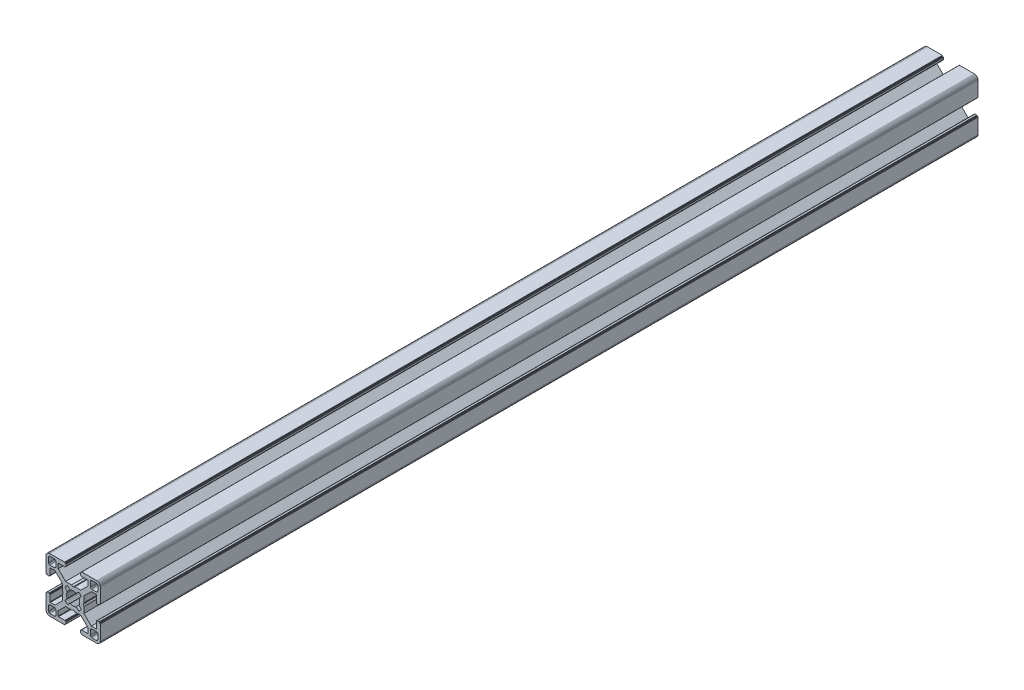
SolidWorks part; units mm, degrees
ref_plane "Front Plane" through (0, 0, 0) normal (0, 0, 1) x (1, 0, 0)
ref_plane "Top Plane" through (0, 0, 0) normal (0, 1, 0) x (1, 0, 0)
ref_plane "Right Plane" through (0, 0, 0) normal (1, 0, 0) x (0, 0, -1)
ref_plane "Plane1" through (0, 0, 0) normal (0, 0, 1) x (1, 0, 0)
sketch "Sketch1" plane through (0, 0, 0) normal (0, 0, 1) x (1, 0, 0)
  line L0 (28.3473, 29.9696) -> (28, 30)
  line L1 (28, 30) -> (19.75, 30)
  line L2 (19.75, 30) -> (19.7153, 29.997)
  line L3 (19.7153, 29.997) -> (19.6816, 29.9879)
  line L4 (19.6816, 29.9879) -> (19.65, 29.9732)
  line L5 (19.65, 29.9732) -> (19.6214, 29.9532)
  line L6 (19.6214, 29.9532) -> (19.5968, 29.9286)
  line L7 (19.5968, 29.9286) -> (19.5768, 29.9)
  line L8 (19.5768, 29.9) -> (19.5621, 29.8684)
  line L9 (19.5621, 29.8684) -> (19.553, 29.8347)
  line L10 (19.553, 29.8347) -> (19.55, 29.8)
  line L11 (19.55, 29.8) -> (19.55, 29.7)
  line L12 (19.55, 29.7) -> (19.547, 29.6653)
  line L13 (19.547, 29.6653) -> (19.5379, 29.6316)
  line L14 (19.5379, 29.6316) -> (19.5232, 29.6)
  line L15 (19.5232, 29.6) -> (19.5032, 29.5714)
  line L16 (19.5032, 29.5714) -> (19.4786, 29.5468)
  line L17 (19.4786, 29.5468) -> (19.45, 29.5268)
  line L18 (19.45, 29.5268) -> (19.4184, 29.5121)
  line L19 (19.4184, 29.5121) -> (19.3847, 29.503)
  line L20 (19.3847, 29.503) -> (19.35, 29.5)
  line L21 (19.35, 29.5) -> (19.25, 29.5)
  line L22 (19.25, 29.5) -> (19.2153, 29.497)
  line L23 (19.2153, 29.497) -> (19.1816, 29.4879)
  line L24 (19.1816, 29.4879) -> (19.15, 29.4732)
  line L25 (19.15, 29.4732) -> (19.1214, 29.4532)
  line L26 (19.1214, 29.4532) -> (19.0968, 29.4286)
  line L27 (19.0968, 29.4286) -> (19.0768, 29.4)
  line L28 (19.0768, 29.4) -> (19.0621, 29.3684)
  line L29 (19.0621, 29.3684) -> (19.053, 29.3347)
  line L30 (19.053, 29.3347) -> (19.05, 29.3)
  line L31 (19.05, 29.3) -> (19.05, 28.4)
  line L32 (19.05, 28.4) -> (19.0591, 28.2958)
  line L33 (19.0591, 28.2958) -> (19.0862, 28.1948)
  line L34 (19.0862, 28.1948) -> (19.1304, 28.1)
  line L35 (19.1304, 28.1) -> (19.1904, 28.0143)
  line L36 (19.1904, 28.0143) -> (19.2643, 27.9404)
  line L37 (19.2643, 27.9404) -> (19.35, 27.8804)
  line L38 (19.35, 27.8804) -> (19.4448, 27.8362)
  line L39 (19.4448, 27.8362) -> (19.5458, 27.8091)
  line L40 (19.5458, 27.8091) -> (19.65, 27.8)
  line L41 (19.65, 27.8) -> (23.05, 27.8)
  line L42 (23.05, 27.8) -> (23.0847, 27.7969)
  line L43 (23.0847, 27.7969) -> (23.1184, 27.7879)
  line L44 (23.1184, 27.7879) -> (23.15, 27.7732)
  line L45 (23.15, 27.7732) -> (23.1786, 27.7532)
  line L46 (23.1786, 27.7532) -> (23.2032, 27.7285)
  line L47 (23.2032, 27.7285) -> (23.2232, 27.7)
  line L48 (23.2232, 27.7) -> (23.2379, 27.6684)
  line L49 (23.2379, 27.6684) -> (23.247, 27.6347)
  line L50 (23.247, 27.6347) -> (23.25, 27.6)
  line L51 (23.25, 27.6) -> (23.25, 25.05)
  line L52 (23.25, 25.05) -> (19.2045, 21)
  line L53 (19.2045, 21) -> (15.9, 21)
  line L54 (15.9, 21) -> (15, 20.4848)
  line L55 (15, 20.4848) -> (14.1, 21)
  line L56 (14.1, 21) -> (10.7955, 21)
  line L57 (10.7955, 21) -> (7.9973, 23.8013)
  line L58 (7.9973, 23.8013) -> (6.75, 25.05)
  line L59 (6.75, 25.05) -> (6.75, 27.6)
  line L60 (6.75, 27.6) -> (6.753, 27.6347)
  line L61 (6.753, 27.6347) -> (6.7621, 27.6684)
  line L62 (6.7621, 27.6684) -> (6.7768, 27.7)
  line L63 (6.7768, 27.7) -> (6.7968, 27.7285)
  line L64 (6.7968, 27.7285) -> (6.8215, 27.7532)
  line L65 (6.8215, 27.7532) -> (6.85, 27.7732)
  line L66 (6.85, 27.7732) -> (6.8816, 27.7879)
  line L67 (6.8816, 27.7879) -> (6.9153, 27.7969)
  line L68 (6.9153, 27.7969) -> (6.95, 27.8)
  line L69 (6.95, 27.8) -> (10.35, 27.8)
  line L70 (10.35, 27.8) -> (10.4542, 27.8091)
  line L71 (10.4542, 27.8091) -> (10.5552, 27.8362)
  line L72 (10.5552, 27.8362) -> (10.65, 27.8804)
  line L73 (10.65, 27.8804) -> (10.7357, 27.9404)
  line L74 (10.7357, 27.9404) -> (10.8096, 28.0143)
  line L75 (10.8096, 28.0143) -> (10.8696, 28.1)
  line L76 (10.8696, 28.1) -> (10.9138, 28.1948)
  line L77 (10.9138, 28.1948) -> (10.9409, 28.2958)
  line L78 (10.9409, 28.2958) -> (10.95, 28.4)
  line L79 (10.95, 28.4) -> (10.95, 29.3)
  line L80 (10.95, 29.3) -> (10.947, 29.3347)
  line L81 (10.947, 29.3347) -> (10.938, 29.3684)
  line L82 (10.938, 29.3684) -> (10.9232, 29.4)
  line L83 (10.9232, 29.4) -> (10.9032, 29.4286)
  line L84 (10.9032, 29.4286) -> (10.8786, 29.4532)
  line L85 (10.8786, 29.4532) -> (10.85, 29.4732)
  line L86 (10.85, 29.4732) -> (10.8184, 29.4879)
  line L87 (10.8184, 29.4879) -> (10.7847, 29.497)
  line L88 (10.7847, 29.497) -> (10.75, 29.5)
  line L89 (10.75, 29.5) -> (10.65, 29.5)
  line L90 (10.65, 29.5) -> (10.6153, 29.503)
  line L91 (10.6153, 29.503) -> (10.5816, 29.5121)
  line L92 (10.5816, 29.5121) -> (10.55, 29.5268)
  line L93 (10.55, 29.5268) -> (10.5214, 29.5468)
  line L94 (10.5214, 29.5468) -> (10.4968, 29.5714)
  line L95 (10.4968, 29.5714) -> (10.4768, 29.6)
  line L96 (10.4768, 29.6) -> (10.4621, 29.6316)
  line L97 (10.4621, 29.6316) -> (10.453, 29.6653)
  line L98 (10.453, 29.6653) -> (10.45, 29.7)
  line L99 (10.45, 29.7) -> (10.45, 29.8)
  line L100 (10.45, 29.8) -> (10.447, 29.8347)
  line L101 (10.447, 29.8347) -> (10.4379, 29.8684)
  line L102 (10.4379, 29.8684) -> (10.4232, 29.9)
  line L103 (10.4232, 29.9) -> (10.4032, 29.9286)
  line L104 (10.4032, 29.9286) -> (10.3786, 29.9532)
  line L105 (10.3786, 29.9532) -> (10.35, 29.9732)
  line L106 (10.35, 29.9732) -> (10.3184, 29.9879)
  line L107 (10.3184, 29.9879) -> (10.2847, 29.997)
  line L108 (10.2847, 29.997) -> (10.25, 30)
  line L109 (10.25, 30) -> (2, 30)
  line L110 (2, 30) -> (1.6527, 29.9696)
  line L111 (1.6527, 29.9696) -> (1.316, 29.8794)
  line L112 (1.316, 29.8794) -> (1, 29.7321)
  line L113 (1, 29.7321) -> (0.7144, 29.5321)
  line L114 (0.7144, 29.5321) -> (0.4679, 29.2856)
  line L115 (0.4679, 29.2856) -> (0.2679, 29)
  line L116 (0.2679, 29) -> (0.1206, 28.684)
  line L117 (0.1206, 28.684) -> (0.0304, 28.3473)
  line L118 (0.0304, 28.3473) -> (0, 28)
  line L119 (0, 28) -> (0, 19.75)
  line L120 (0, 19.75) -> (0.003, 19.7153)
  line L121 (0.003, 19.7153) -> (0.0121, 19.6816)
  line L122 (0.0121, 19.6816) -> (0.0268, 19.65)
  line L123 (0.0268, 19.65) -> (0.0468, 19.6214)
  line L124 (0.0468, 19.6214) -> (0.0714, 19.5968)
  line L125 (0.0714, 19.5968) -> (0.1, 19.5768)
  line L126 (0.1, 19.5768) -> (0.1316, 19.5621)
  line L127 (0.1316, 19.5621) -> (0.1653, 19.553)
  line L128 (0.1653, 19.553) -> (0.2, 19.55)
  line L129 (0.2, 19.55) -> (0.3, 19.55)
  line L130 (0.3, 19.55) -> (0.3347, 19.547)
  line L131 (0.3347, 19.547) -> (0.3684, 19.5379)
  line L132 (0.3684, 19.5379) -> (0.4, 19.5232)
  line L133 (0.4, 19.5232) -> (0.4286, 19.5032)
  line L134 (0.4286, 19.5032) -> (0.4532, 19.4786)
  line L135 (0.4532, 19.4786) -> (0.4732, 19.45)
  line L136 (0.4732, 19.45) -> (0.4879, 19.4184)
  line L137 (0.4879, 19.4184) -> (0.497, 19.3847)
  line L138 (0.497, 19.3847) -> (0.5, 19.35)
  line L139 (0.5, 19.35) -> (0.5, 19.25)
  line L140 (0.5, 19.25) -> (0.503, 19.2153)
  line L141 (0.503, 19.2153) -> (0.5121, 19.1816)
  line L142 (0.5121, 19.1816) -> (0.5268, 19.15)
  line L143 (0.5268, 19.15) -> (0.5468, 19.1214)
  line L144 (0.5468, 19.1214) -> (0.5714, 19.0968)
  line L145 (0.5714, 19.0968) -> (0.6, 19.0768)
  line L146 (0.6, 19.0768) -> (0.6316, 19.0621)
  line L147 (0.6316, 19.0621) -> (0.6653, 19.053)
  line L148 (0.6653, 19.053) -> (0.7, 19.05)
  line L149 (0.7, 19.05) -> (1.6, 19.05)
  line L150 (1.6, 19.05) -> (1.7042, 19.0591)
  line L151 (1.7042, 19.0591) -> (1.8052, 19.0862)
  line L152 (1.8052, 19.0862) -> (1.9, 19.1304)
  line L153 (1.9, 19.1304) -> (1.9857, 19.1904)
  line L154 (1.9857, 19.1904) -> (2.0596, 19.2643)
  line L155 (2.0596, 19.2643) -> (2.1196, 19.35)
  line L156 (2.1196, 19.35) -> (2.1638, 19.4448)
  line L157 (2.1638, 19.4448) -> (2.1909, 19.5458)
  line L158 (2.1909, 19.5458) -> (2.2, 19.65)
  line L159 (2.2, 19.65) -> (2.2, 23.05)
  line L160 (2.2, 23.05) -> (2.203, 23.0847)
  line L161 (2.203, 23.0847) -> (2.2121, 23.1184)
  line L162 (2.2121, 23.1184) -> (2.2268, 23.15)
  line L163 (2.2268, 23.15) -> (2.2468, 23.1786)
  line L164 (2.2468, 23.1786) -> (2.2714, 23.2032)
  line L165 (2.2714, 23.2032) -> (2.3, 23.2232)
  line L166 (2.3, 23.2232) -> (2.3316, 23.2379)
  line L167 (2.3316, 23.2379) -> (2.3653, 23.247)
  line L168 (2.3653, 23.247) -> (2.4, 23.25)
  line L169 (2.4, 23.25) -> (4.95, 23.25)
  line L170 (4.95, 23.25) -> (7.9973, 20.2027)
  line L171 (7.9973, 20.2027) -> (8.9955, 19.2045)
  line L172 (8.9955, 19.2045) -> (8.9955, 15.9)
  line L173 (8.9955, 15.9) -> (9.5151, 15)
  line L174 (9.5151, 15) -> (8.9955, 14.1)
  line L175 (8.9955, 14.1) -> (8.9955, 10.7955)
  line L176 (8.9955, 10.7955) -> (4.95, 6.75)
  line L177 (4.95, 6.75) -> (2.4, 6.75)
  line L178 (2.4, 6.75) -> (2.3653, 6.753)
  line L179 (2.3653, 6.753) -> (2.3316, 6.7621)
  line L180 (2.3316, 6.7621) -> (2.3, 6.7768)
  line L181 (2.3, 6.7768) -> (2.2714, 6.7968)
  line L182 (2.2714, 6.7968) -> (2.2468, 6.8214)
  line L183 (2.2468, 6.8214) -> (2.2268, 6.85)
  line L184 (2.2268, 6.85) -> (2.2121, 6.8816)
  line L185 (2.2121, 6.8816) -> (2.203, 6.9153)
  line L186 (2.203, 6.9153) -> (2.2, 6.95)
  line L187 (2.2, 6.95) -> (2.2, 10.35)
  line L188 (2.2, 10.35) -> (2.1909, 10.4542)
  line L189 (2.1909, 10.4542) -> (2.1638, 10.5552)
  line L190 (2.1638, 10.5552) -> (2.1196, 10.65)
  line L191 (2.1196, 10.65) -> (2.0596, 10.7357)
  line L192 (2.0596, 10.7357) -> (1.9857, 10.8096)
  line L193 (1.9857, 10.8096) -> (1.9, 10.8696)
  line L194 (1.9, 10.8696) -> (1.8052, 10.9138)
  line L195 (1.8052, 10.9138) -> (1.7042, 10.9409)
  line L196 (1.7042, 10.9409) -> (1.6, 10.95)
  line L197 (1.6, 10.95) -> (0.7, 10.95)
  line L198 (0.7, 10.95) -> (0.6653, 10.9469)
  line L199 (0.6653, 10.9469) -> (0.6316, 10.9379)
  line L200 (0.6316, 10.9379) -> (0.6, 10.9232)
  line L201 (0.6, 10.9232) -> (0.5715, 10.9032)
  line L202 (0.5715, 10.9032) -> (0.5468, 10.8785)
  line L203 (0.5468, 10.8785) -> (0.5268, 10.85)
  line L204 (0.5268, 10.85) -> (0.5121, 10.8184)
  line L205 (0.5121, 10.8184) -> (0.503, 10.7847)
  line L206 (0.503, 10.7847) -> (0.5, 10.75)
  line L207 (0.5, 10.75) -> (0.5, 10.65)
  line L208 (0.5, 10.65) -> (0.497, 10.6153)
  line L209 (0.497, 10.6153) -> (0.4879, 10.5816)
  line L210 (0.4879, 10.5816) -> (0.4732, 10.55)
  line L211 (0.4732, 10.55) -> (0.4532, 10.5214)
  line L212 (0.4532, 10.5214) -> (0.4286, 10.4968)
  line L213 (0.4286, 10.4968) -> (0.4, 10.4768)
  line L214 (0.4, 10.4768) -> (0.3684, 10.4621)
  line L215 (0.3684, 10.4621) -> (0.3347, 10.453)
  line L216 (0.3347, 10.453) -> (0.3, 10.45)
  line L217 (0.3, 10.45) -> (0.2, 10.45)
  line L218 (0.2, 10.45) -> (0.1653, 10.447)
  line L219 (0.1653, 10.447) -> (0.1316, 10.4379)
  line L220 (0.1316, 10.4379) -> (0.1, 10.4232)
  line L221 (0.1, 10.4232) -> (0.0714, 10.4032)
  line L222 (0.0714, 10.4032) -> (0.0468, 10.3786)
  line L223 (0.0468, 10.3786) -> (0.0268, 10.35)
  line L224 (0.0268, 10.35) -> (0.0121, 10.3184)
  line L225 (0.0121, 10.3184) -> (0.003, 10.2847)
  line L226 (0.003, 10.2847) -> (0, 10.25)
  line L227 (0, 10.25) -> (0, 2)
  line L228 (0, 2) -> (0.0304, 1.6527)
  line L229 (0.0304, 1.6527) -> (0.1206, 1.316)
  line L230 (0.1206, 1.316) -> (0.2679, 1)
  line L231 (0.2679, 1) -> (0.4679, 0.7144)
  line L232 (0.4679, 0.7144) -> (0.7144, 0.4679)
  line L233 (0.7144, 0.4679) -> (1, 0.2679)
  line L234 (1, 0.2679) -> (1.316, 0.1206)
  line L235 (1.316, 0.1206) -> (1.6527, 0.0304)
  line L236 (1.6527, 0.0304) -> (2, 0)
  line L237 (2, 0) -> (10.25, 0)
  line L238 (10.25, 0) -> (10.2847, 0.003)
  line L239 (10.2847, 0.003) -> (10.3184, 0.0121)
  line L240 (10.3184, 0.0121) -> (10.35, 0.0268)
  line L241 (10.35, 0.0268) -> (10.3786, 0.0468)
  line L242 (10.3786, 0.0468) -> (10.4032, 0.0714)
  line L243 (10.4032, 0.0714) -> (10.4232, 0.1)
  line L244 (10.4232, 0.1) -> (10.4379, 0.1316)
  line L245 (10.4379, 0.1316) -> (10.447, 0.1653)
  line L246 (10.447, 0.1653) -> (10.45, 0.2)
  line L247 (10.45, 0.2) -> (10.45, 0.3)
  line L248 (10.45, 0.3) -> (10.453, 0.3347)
  line L249 (10.453, 0.3347) -> (10.4621, 0.3684)
  line L250 (10.4621, 0.3684) -> (10.4768, 0.4)
  line L251 (10.4768, 0.4) -> (10.4968, 0.4286)
  line L252 (10.4968, 0.4286) -> (10.5214, 0.4532)
  line L253 (10.5214, 0.4532) -> (10.55, 0.4732)
  line L254 (10.55, 0.4732) -> (10.5816, 0.4879)
  line L255 (10.5816, 0.4879) -> (10.6153, 0.497)
  line L256 (10.6153, 0.497) -> (10.65, 0.5)
  line L257 (10.65, 0.5) -> (10.75, 0.5)
  line L258 (10.75, 0.5) -> (10.7847, 0.503)
  line L259 (10.7847, 0.503) -> (10.8184, 0.5121)
  line L260 (10.8184, 0.5121) -> (10.85, 0.5268)
  line L261 (10.85, 0.5268) -> (10.8785, 0.5468)
  line L262 (10.8785, 0.5468) -> (10.9032, 0.5715)
  line L263 (10.9032, 0.5715) -> (10.9232, 0.6)
  line L264 (10.9232, 0.6) -> (10.9379, 0.6316)
  line L265 (10.9379, 0.6316) -> (10.9469, 0.6653)
  line L266 (10.9469, 0.6653) -> (10.95, 0.7)
  line L267 (10.95, 0.7) -> (10.95, 1.6)
  line L268 (10.95, 1.6) -> (10.9409, 1.7042)
  line L269 (10.9409, 1.7042) -> (10.9138, 1.8052)
  line L270 (10.9138, 1.8052) -> (10.8696, 1.9)
  line L271 (10.8696, 1.9) -> (10.8096, 1.9857)
  line L272 (10.8096, 1.9857) -> (10.7357, 2.0596)
  line L273 (10.7357, 2.0596) -> (10.65, 2.1196)
  line L274 (10.65, 2.1196) -> (10.5552, 2.1638)
  line L275 (10.5552, 2.1638) -> (10.4542, 2.1909)
  line L276 (10.4542, 2.1909) -> (10.35, 2.2)
  line L277 (10.35, 2.2) -> (6.95, 2.2)
  line L278 (6.95, 2.2) -> (6.9153, 2.203)
  line L279 (6.9153, 2.203) -> (6.8816, 2.212)
  line L280 (6.8816, 2.212) -> (6.85, 2.2268)
  line L281 (6.85, 2.2268) -> (6.8215, 2.2468)
  line L282 (6.8215, 2.2468) -> (6.7968, 2.2714)
  line L283 (6.7968, 2.2714) -> (6.7768, 2.3)
  line L284 (6.7768, 2.3) -> (6.7621, 2.3316)
  line L285 (6.7621, 2.3316) -> (6.753, 2.3653)
  line L286 (6.753, 2.3653) -> (6.75, 2.4)
  line L287 (6.75, 2.4) -> (6.75, 4.95)
  line L288 (6.75, 4.95) -> (9.7875, 7.9908)
  line L289 (9.7875, 7.9908) -> (10.7955, 9)
  line L290 (10.7955, 9) -> (14.1, 9)
  line L291 (14.1, 9) -> (15, 9.5151)
  line L292 (15, 9.5151) -> (15.9, 9)
  line L293 (15.9, 9) -> (19.2045, 9)
  line L294 (19.2045, 9) -> (20.2126, 7.9908)
  line L295 (20.2126, 7.9908) -> (23.25, 4.95)
  line L296 (23.25, 4.95) -> (23.25, 2.4)
  line L297 (23.25, 2.4) -> (23.247, 2.3653)
  line L298 (23.247, 2.3653) -> (23.2379, 2.3316)
  line L299 (23.2379, 2.3316) -> (23.2232, 2.3)
  line L300 (23.2232, 2.3) -> (23.2032, 2.2714)
  line L301 (23.2032, 2.2714) -> (23.1786, 2.2468)
  line L302 (23.1786, 2.2468) -> (23.15, 2.2268)
  line L303 (23.15, 2.2268) -> (23.1184, 2.212)
  line L304 (23.1184, 2.212) -> (23.0847, 2.203)
  line L305 (23.0847, 2.203) -> (23.05, 2.2)
  line L306 (23.05, 2.2) -> (19.65, 2.2)
  line L307 (19.65, 2.2) -> (19.5458, 2.1909)
  line L308 (19.5458, 2.1909) -> (19.4448, 2.1638)
  line L309 (19.4448, 2.1638) -> (19.35, 2.1196)
  line L310 (19.35, 2.1196) -> (19.2643, 2.0596)
  line L311 (19.2643, 2.0596) -> (19.1904, 1.9857)
  line L312 (19.1904, 1.9857) -> (19.1304, 1.9)
  line L313 (19.1304, 1.9) -> (19.0862, 1.8052)
  line L314 (19.0862, 1.8052) -> (19.0591, 1.7042)
  line L315 (19.0591, 1.7042) -> (19.05, 1.6)
  line L316 (19.05, 1.6) -> (19.05, 0.7)
  line L317 (19.05, 0.7) -> (19.053, 0.6653)
  line L318 (19.053, 0.6653) -> (19.0621, 0.6316)
  line L319 (19.0621, 0.6316) -> (19.0768, 0.6)
  line L320 (19.0768, 0.6) -> (19.0968, 0.5714)
  line L321 (19.0968, 0.5714) -> (19.1214, 0.5468)
  line L322 (19.1214, 0.5468) -> (19.15, 0.5268)
  line L323 (19.15, 0.5268) -> (19.1816, 0.5121)
  line L324 (19.1816, 0.5121) -> (19.2153, 0.503)
  line L325 (19.2153, 0.503) -> (19.25, 0.5)
  line L326 (19.25, 0.5) -> (19.35, 0.5)
  line L327 (19.35, 0.5) -> (19.3847, 0.497)
  line L328 (19.3847, 0.497) -> (19.4184, 0.4879)
  line L329 (19.4184, 0.4879) -> (19.45, 0.4732)
  line L330 (19.45, 0.4732) -> (19.4786, 0.4532)
  line L331 (19.4786, 0.4532) -> (19.5032, 0.4286)
  line L332 (19.5032, 0.4286) -> (19.5232, 0.4)
  line L333 (19.5232, 0.4) -> (19.5379, 0.3684)
  line L334 (19.5379, 0.3684) -> (19.547, 0.3347)
  line L335 (19.547, 0.3347) -> (19.55, 0.3)
  line L336 (19.55, 0.3) -> (19.55, 0.2)
  line L337 (19.55, 0.2) -> (19.553, 0.1653)
  line L338 (19.553, 0.1653) -> (19.5621, 0.1316)
  line L339 (19.5621, 0.1316) -> (19.5768, 0.1)
  line L340 (19.5768, 0.1) -> (19.5968, 0.0714)
  line L341 (19.5968, 0.0714) -> (19.6214, 0.0468)
  line L342 (19.6214, 0.0468) -> (19.65, 0.0268)
  line L343 (19.65, 0.0268) -> (19.6816, 0.0121)
  line L344 (19.6816, 0.0121) -> (19.7153, 0.003)
  line L345 (19.7153, 0.003) -> (19.75, 0)
  line L346 (19.75, 0) -> (28, 0)
  line L347 (28, 0) -> (28.3473, 0.0304)
  line L348 (28.3473, 0.0304) -> (28.684, 0.1206)
  line L349 (28.684, 0.1206) -> (29, 0.2679)
  line L350 (29, 0.2679) -> (29.2856, 0.4679)
  line L351 (29.2856, 0.4679) -> (29.5321, 0.7144)
  line L352 (29.5321, 0.7144) -> (29.7321, 1)
  line L353 (29.7321, 1) -> (29.8794, 1.316)
  line L354 (29.8794, 1.316) -> (29.9696, 1.6527)
  line L355 (29.9696, 1.6527) -> (30, 2)
  line L356 (30, 2) -> (30, 10.25)
  line L357 (30, 10.25) -> (29.997, 10.2847)
  line L358 (29.997, 10.2847) -> (29.988, 10.3184)
  line L359 (29.988, 10.3184) -> (29.9732, 10.35)
  line L360 (29.9732, 10.35) -> (29.9532, 10.3785)
  line L361 (29.9532, 10.3785) -> (29.9286, 10.4032)
  line L362 (29.9286, 10.4032) -> (29.9, 10.4232)
  line L363 (29.9, 10.4232) -> (29.8684, 10.4379)
  line L364 (29.8684, 10.4379) -> (29.8347, 10.447)
  line L365 (29.8347, 10.447) -> (29.8, 10.45)
  line L366 (29.8, 10.45) -> (29.7, 10.45)
  line L367 (29.7, 10.45) -> (29.6649, 10.4534)
  line L368 (29.6649, 10.4534) -> (29.6312, 10.4624)
  line L369 (29.6312, 10.4624) -> (29.5996, 10.4772)
  line L370 (29.5996, 10.4772) -> (29.5711, 10.4972)
  line L371 (29.5711, 10.4972) -> (29.5464, 10.5218)
  line L372 (29.5464, 10.5218) -> (29.5264, 10.5504)
  line L373 (29.5264, 10.5504) -> (29.5117, 10.582)
  line L374 (29.5117, 10.582) -> (29.5027, 10.6156)
  line L375 (29.5027, 10.6156) -> (29.4996, 10.6504)
  line L376 (29.4996, 10.6504) -> (29.4996, 10.7504)
  line L377 (29.4996, 10.7504) -> (29.497, 10.7847)
  line L378 (29.497, 10.7847) -> (29.4879, 10.8184)
  line L379 (29.4879, 10.8184) -> (29.4732, 10.85)
  line L380 (29.4732, 10.85) -> (29.4532, 10.8785)
  line L381 (29.4532, 10.8785) -> (29.4286, 10.9032)
  line L382 (29.4286, 10.9032) -> (29.4, 10.9232)
  line L383 (29.4, 10.9232) -> (29.3684, 10.9379)
  line L384 (29.3684, 10.9379) -> (29.3347, 10.9469)
  line L385 (29.3347, 10.9469) -> (29.3, 10.95)
  line L386 (29.3, 10.95) -> (28.4, 10.95)
  line L387 (28.4, 10.95) -> (28.2958, 10.9409)
  line L388 (28.2958, 10.9409) -> (28.1948, 10.9138)
  line L389 (28.1948, 10.9138) -> (28.1, 10.8696)
  line L390 (28.1, 10.8696) -> (28.0143, 10.8096)
  line L391 (28.0143, 10.8096) -> (27.9404, 10.7357)
  line L392 (27.9404, 10.7357) -> (27.8804, 10.65)
  line L393 (27.8804, 10.65) -> (27.8362, 10.5552)
  line L394 (27.8362, 10.5552) -> (27.8091, 10.4542)
  line L395 (27.8091, 10.4542) -> (27.8, 10.35)
  line L396 (27.8, 10.35) -> (27.8, 6.95)
  line L397 (27.8, 6.95) -> (27.797, 6.9153)
  line L398 (27.797, 6.9153) -> (27.7879, 6.8816)
  line L399 (27.7879, 6.8816) -> (27.7732, 6.85)
  line L400 (27.7732, 6.85) -> (27.7532, 6.8214)
  line L401 (27.7532, 6.8214) -> (27.7286, 6.7968)
  line L402 (27.7286, 6.7968) -> (27.7, 6.7768)
  line L403 (27.7, 6.7768) -> (27.6684, 6.7621)
  line L404 (27.6684, 6.7621) -> (27.6347, 6.753)
  line L405 (27.6347, 6.753) -> (27.6, 6.75)
  line L406 (27.6, 6.75) -> (25.05, 6.75)
  line L407 (25.05, 6.75) -> (23.8092, 7.9908)
  line L408 (23.8092, 7.9908) -> (21.0045, 10.7955)
  line L409 (21.0045, 10.7955) -> (21.0045, 14.1)
  line L410 (21.0045, 14.1) -> (20.4849, 15)
  line L411 (20.4849, 15) -> (21.0045, 15.9)
  line L412 (21.0045, 15.9) -> (21.0045, 19.2045)
  line L413 (21.0045, 19.2045) -> (25.05, 23.25)
  line L414 (25.05, 23.25) -> (27.6, 23.25)
  line L415 (27.6, 23.25) -> (27.6347, 23.247)
  line L416 (27.6347, 23.247) -> (27.6684, 23.2379)
  line L417 (27.6684, 23.2379) -> (27.7, 23.2232)
  line L418 (27.7, 23.2232) -> (27.7286, 23.2032)
  line L419 (27.7286, 23.2032) -> (27.7532, 23.1786)
  line L420 (27.7532, 23.1786) -> (27.7732, 23.15)
  line L421 (27.7732, 23.15) -> (27.7879, 23.1184)
  line L422 (27.7879, 23.1184) -> (27.797, 23.0847)
  line L423 (27.797, 23.0847) -> (27.8, 23.05)
  line L424 (27.8, 23.05) -> (27.8, 19.65)
  line L425 (27.8, 19.65) -> (27.8091, 19.5458)
  line L426 (27.8091, 19.5458) -> (27.8362, 19.4448)
  line L427 (27.8362, 19.4448) -> (27.8804, 19.35)
  line L428 (27.8804, 19.35) -> (27.9404, 19.2643)
  line L429 (27.9404, 19.2643) -> (28.0143, 19.1904)
  line L430 (28.0143, 19.1904) -> (28.1, 19.1304)
  line L431 (28.1, 19.1304) -> (28.1948, 19.0862)
  line L432 (28.1948, 19.0862) -> (28.2958, 19.0591)
  line L433 (28.2958, 19.0591) -> (28.4, 19.05)
  line L434 (28.4, 19.05) -> (29.3, 19.05)
  line L435 (29.3, 19.05) -> (29.3347, 19.053)
  line L436 (29.3347, 19.053) -> (29.3684, 19.0621)
  line L437 (29.3684, 19.0621) -> (29.4, 19.0768)
  line L438 (29.4, 19.0768) -> (29.4282, 19.0971)
  line L439 (29.4282, 19.0971) -> (29.4528, 19.1218)
  line L440 (29.4528, 19.1218) -> (29.4728, 19.1504)
  line L441 (29.4728, 19.1504) -> (29.4876, 19.182)
  line L442 (29.4876, 19.182) -> (29.4966, 19.2156)
  line L443 (29.4966, 19.2156) -> (29.4996, 19.2504)
  line L444 (29.4996, 19.2504) -> (29.4996, 19.3504)
  line L445 (29.4996, 19.3504) -> (29.5027, 19.3851)
  line L446 (29.5027, 19.3851) -> (29.5117, 19.4188)
  line L447 (29.5117, 19.4188) -> (29.5264, 19.4504)
  line L448 (29.5264, 19.4504) -> (29.5464, 19.4789)
  line L449 (29.5464, 19.4789) -> (29.5711, 19.5036)
  line L450 (29.5711, 19.5036) -> (29.5996, 19.5236)
  line L451 (29.5996, 19.5236) -> (29.6312, 19.5383)
  line L452 (29.6312, 19.5383) -> (29.6649, 19.5473)
  line L453 (29.6649, 19.5473) -> (29.7, 19.55)
  line L454 (29.7, 19.55) -> (29.8, 19.55)
  line L455 (29.8, 19.55) -> (29.8347, 19.553)
  line L456 (29.8347, 19.553) -> (29.8684, 19.5621)
  line L457 (29.8684, 19.5621) -> (29.9, 19.5768)
  line L458 (29.9, 19.5768) -> (29.9286, 19.5968)
  line L459 (29.9286, 19.5968) -> (29.9532, 19.6214)
  line L460 (29.9532, 19.6214) -> (29.9732, 19.65)
  line L461 (29.9732, 19.65) -> (29.9879, 19.6816)
  line L462 (29.9879, 19.6816) -> (29.997, 19.7153)
  line L463 (29.997, 19.7153) -> (30, 19.75)
  line L464 (30, 19.75) -> (30, 28)
  line L465 (30, 28) -> (29.9696, 28.3473)
  line L466 (29.9696, 28.3473) -> (29.8794, 28.684)
  line L467 (29.8794, 28.684) -> (29.7321, 29)
  line L468 (29.7321, 29) -> (29.5321, 29.2856)
  line L469 (29.5321, 29.2856) -> (29.2856, 29.5321)
  line L470 (29.2856, 29.5321) -> (29, 29.7321)
  line L471 (29, 29.7321) -> (28.684, 29.8794)
  line L472 (28.684, 29.8794) -> (28.3473, 29.9696)
  line L473 (1.3, 25.5) -> (1.3, 27.7)
  line L474 (1.3, 27.7) -> (1.3123, 27.8564)
  line L475 (1.3123, 27.8564) -> (1.3489, 28.009)
  line L476 (1.3489, 28.009) -> (1.409, 28.154)
  line L477 (1.409, 28.154) -> (1.491, 28.2878)
  line L478 (1.491, 28.2878) -> (1.5929, 28.4071)
  line L479 (1.5929, 28.4071) -> (1.7122, 28.509)
  line L480 (1.7122, 28.509) -> (1.846, 28.591)
  line L481 (1.846, 28.591) -> (1.991, 28.6511)
  line L482 (1.991, 28.6511) -> (2.1436, 28.6877)
  line L483 (2.1436, 28.6877) -> (2.3, 28.7)
  line L484 (2.3, 28.7) -> (4.5, 28.7)
  line L485 (4.5, 28.7) -> (4.6564, 28.6877)
  line L486 (4.6564, 28.6877) -> (4.809, 28.6511)
  line L487 (4.809, 28.6511) -> (4.954, 28.591)
  line L488 (4.954, 28.591) -> (5.0878, 28.509)
  line L489 (5.0878, 28.509) -> (5.2071, 28.4071)
  line L490 (5.2071, 28.4071) -> (5.309, 28.2878)
  line L491 (5.309, 28.2878) -> (5.391, 28.154)
  line L492 (5.391, 28.154) -> (5.4511, 28.009)
  line L493 (5.4511, 28.009) -> (5.4877, 27.8564)
  line L494 (5.4877, 27.8564) -> (5.5, 27.7)
  line L495 (5.5, 27.7) -> (5.5, 25.5)
  line L496 (5.5, 25.5) -> (5.4877, 25.3436)
  line L497 (5.4877, 25.3436) -> (5.4511, 25.191)
  line L498 (5.4511, 25.191) -> (5.391, 25.046)
  line L499 (5.391, 25.046) -> (5.309, 24.9122)
  line L500 (5.309, 24.9122) -> (5.2071, 24.7929)
  line L501 (5.2071, 24.7929) -> (5.0878, 24.691)
  line L502 (5.0878, 24.691) -> (4.954, 24.609)
  line L503 (4.954, 24.609) -> (4.809, 24.5489)
  line L504 (4.809, 24.5489) -> (4.6564, 24.5123)
  line L505 (4.6564, 24.5123) -> (4.5, 24.5)
  line L506 (4.5, 24.5) -> (2.3, 24.5)
  line L507 (2.3, 24.5) -> (2.1436, 24.5123)
  line L508 (2.1436, 24.5123) -> (1.991, 24.5489)
  line L509 (1.991, 24.5489) -> (1.846, 24.609)
  line L510 (1.846, 24.609) -> (1.7122, 24.691)
  line L511 (1.7122, 24.691) -> (1.5929, 24.7929)
  line L512 (1.5929, 24.7929) -> (1.491, 24.9122)
  line L513 (1.491, 24.9122) -> (1.409, 25.046)
  line L514 (1.409, 25.046) -> (1.3489, 25.191)
  line L515 (1.3489, 25.191) -> (1.3123, 25.3436)
  line L516 (1.3123, 25.3436) -> (1.3, 25.5)
  line L517 (25.3436, 28.6877) -> (25.5, 28.7)
  line L518 (25.5, 28.7) -> (27.7, 28.7)
  line L519 (27.7, 28.7) -> (27.8564, 28.6877)
  line L520 (27.8564, 28.6877) -> (28.009, 28.6511)
  line L521 (28.009, 28.6511) -> (28.154, 28.591)
  line L522 (28.154, 28.591) -> (28.2878, 28.509)
  line L523 (28.2878, 28.509) -> (28.4071, 28.4071)
  line L524 (28.4071, 28.4071) -> (28.509, 28.2878)
  line L525 (28.509, 28.2878) -> (28.591, 28.154)
  line L526 (28.591, 28.154) -> (28.6511, 28.009)
  line L527 (28.6511, 28.009) -> (28.6877, 27.8564)
  line L528 (28.6877, 27.8564) -> (28.7, 27.7)
  line L529 (28.7, 27.7) -> (28.7, 25.5)
  line L530 (28.7, 25.5) -> (28.6877, 25.3436)
  line L531 (28.6877, 25.3436) -> (28.6511, 25.191)
  line L532 (28.6511, 25.191) -> (28.591, 25.046)
  line L533 (28.591, 25.046) -> (28.509, 24.9122)
  line L534 (28.509, 24.9122) -> (28.4071, 24.7929)
  line L535 (28.4071, 24.7929) -> (28.2878, 24.691)
  line L536 (28.2878, 24.691) -> (28.154, 24.609)
  line L537 (28.154, 24.609) -> (28.009, 24.5489)
  line L538 (28.009, 24.5489) -> (27.8564, 24.5123)
  line L539 (27.8564, 24.5123) -> (27.7, 24.5)
  line L540 (27.7, 24.5) -> (25.5, 24.5)
  line L541 (25.5, 24.5) -> (25.3436, 24.5123)
  line L542 (25.3436, 24.5123) -> (25.191, 24.5489)
  line L543 (25.191, 24.5489) -> (25.046, 24.609)
  line L544 (25.046, 24.609) -> (24.9122, 24.691)
  line L545 (24.9122, 24.691) -> (24.7929, 24.7929)
  line L546 (24.7929, 24.7929) -> (24.691, 24.9122)
  line L547 (24.691, 24.9122) -> (24.609, 25.046)
  line L548 (24.609, 25.046) -> (24.5489, 25.191)
  line L549 (24.5489, 25.191) -> (24.5123, 25.3436)
  line L550 (24.5123, 25.3436) -> (24.5, 25.5)
  line L551 (24.5, 25.5) -> (24.5, 27.7)
  line L552 (24.5, 27.7) -> (24.5123, 27.8564)
  line L553 (24.5123, 27.8564) -> (24.5489, 28.009)
  line L554 (24.5489, 28.009) -> (24.609, 28.154)
  line L555 (24.609, 28.154) -> (24.691, 28.2878)
  line L556 (24.691, 28.2878) -> (24.7929, 28.4071)
  line L557 (24.7929, 28.4071) -> (24.9122, 28.509)
  line L558 (24.9122, 28.509) -> (25.046, 28.591)
  line L559 (25.046, 28.591) -> (25.191, 28.6511)
  line L560 (25.191, 28.6511) -> (25.3436, 28.6877)
  line L561 (15, 18.65) -> (15.55, 18.6083)
  line L562 (15.55, 18.6083) -> (16.0875, 18.4842)
  line L563 (16.0875, 18.4842) -> (16.6001, 18.2806)
  line L564 (16.6001, 18.2806) -> (18.1359, 19.5184)
  line L565 (18.1359, 19.5184) -> (18.645, 19.1187)
  line L566 (18.645, 19.1187) -> (19.1036, 18.6621)
  line L567 (19.1036, 18.6621) -> (19.5053, 18.1547)
  line L568 (19.5053, 18.1547) -> (18.2806, 16.6001)
  line L569 (18.2806, 16.6001) -> (18.4842, 16.0875)
  line L570 (18.4842, 16.0875) -> (18.6083, 15.55)
  line L571 (18.6083, 15.55) -> (18.65, 15)
  line L572 (18.65, 15) -> (18.6083, 14.45)
  line L573 (18.6083, 14.45) -> (18.4842, 13.9125)
  line L574 (18.4842, 13.9125) -> (18.2806, 13.3999)
  line L575 (18.2806, 13.3999) -> (19.5053, 11.8453)
  line L576 (19.5053, 11.8453) -> (19.1036, 11.3379)
  line L577 (19.1036, 11.3379) -> (18.645, 10.8813)
  line L578 (18.645, 10.8813) -> (18.1359, 10.4816)
  line L579 (18.1359, 10.4816) -> (16.6001, 11.7194)
  line L580 (16.6001, 11.7194) -> (16.0875, 11.5158)
  line L581 (16.0875, 11.5158) -> (15.55, 11.3917)
  line L582 (15.55, 11.3917) -> (15, 11.35)
  line L583 (15, 11.35) -> (14.45, 11.3917)
  line L584 (14.45, 11.3917) -> (13.9125, 11.5158)
  line L585 (13.9125, 11.5158) -> (13.3999, 11.7194)
  line L586 (13.3999, 11.7194) -> (11.8641, 10.4816)
  line L587 (11.8641, 10.4816) -> (11.355, 10.8813)
  line L588 (11.355, 10.8813) -> (10.8964, 11.3379)
  line L589 (10.8964, 11.3379) -> (10.4947, 11.8453)
  line L590 (10.4947, 11.8453) -> (11.7194, 13.3999)
  line L591 (11.7194, 13.3999) -> (11.5158, 13.9125)
  line L592 (11.5158, 13.9125) -> (11.3917, 14.45)
  line L593 (11.3917, 14.45) -> (11.35, 15)
  line L594 (11.35, 15) -> (11.3917, 15.55)
  line L595 (11.3917, 15.55) -> (11.5158, 16.0875)
  line L596 (11.5158, 16.0875) -> (11.7194, 16.6001)
  line L597 (11.7194, 16.6001) -> (10.4947, 18.1547)
  line L598 (10.4947, 18.1547) -> (10.8964, 18.6621)
  line L599 (10.8964, 18.6621) -> (11.355, 19.1187)
  line L600 (11.355, 19.1187) -> (11.8641, 19.5184)
  line L601 (11.8641, 19.5184) -> (13.3999, 18.2806)
  line L602 (13.3999, 18.2806) -> (13.9125, 18.4842)
  line L603 (13.9125, 18.4842) -> (14.45, 18.6083)
  line L604 (14.45, 18.6083) -> (15, 18.65)
  line L605 (4.5, 1.3) -> (2.3, 1.3)
  line L606 (2.3, 1.3) -> (2.1436, 1.3123)
  line L607 (2.1436, 1.3123) -> (1.991, 1.3489)
  line L608 (1.991, 1.3489) -> (1.846, 1.409)
  line L609 (1.846, 1.409) -> (1.7122, 1.491)
  line L610 (1.7122, 1.491) -> (1.5929, 1.5929)
  line L611 (1.5929, 1.5929) -> (1.491, 1.7122)
  line L612 (1.491, 1.7122) -> (1.409, 1.846)
  line L613 (1.409, 1.846) -> (1.3489, 1.991)
  line L614 (1.3489, 1.991) -> (1.3123, 2.1436)
  line L615 (1.3123, 2.1436) -> (1.3, 2.3)
  line L616 (1.3, 2.3) -> (1.3, 4.5)
  line L617 (1.3, 4.5) -> (1.3123, 4.6564)
  line L618 (1.3123, 4.6564) -> (1.3489, 4.809)
  line L619 (1.3489, 4.809) -> (1.409, 4.954)
  line L620 (1.409, 4.954) -> (1.491, 5.0878)
  line L621 (1.491, 5.0878) -> (1.5929, 5.2071)
  line L622 (1.5929, 5.2071) -> (1.7122, 5.309)
  line L623 (1.7122, 5.309) -> (1.846, 5.391)
  line L624 (1.846, 5.391) -> (1.991, 5.4511)
  line L625 (1.991, 5.4511) -> (2.1436, 5.4877)
  line L626 (2.1436, 5.4877) -> (2.3, 5.5)
  line L627 (2.3, 5.5) -> (4.5, 5.5)
  line L628 (4.5, 5.5) -> (4.6564, 5.4877)
  line L629 (4.6564, 5.4877) -> (4.809, 5.4511)
  line L630 (4.809, 5.4511) -> (4.954, 5.391)
  line L631 (4.954, 5.391) -> (5.0878, 5.309)
  line L632 (5.0878, 5.309) -> (5.2071, 5.2071)
  line L633 (5.2071, 5.2071) -> (5.309, 5.0878)
  line L634 (5.309, 5.0878) -> (5.391, 4.954)
  line L635 (5.391, 4.954) -> (5.4511, 4.809)
  line L636 (5.4511, 4.809) -> (5.4877, 4.6564)
  line L637 (5.4877, 4.6564) -> (5.5, 4.5)
  line L638 (5.5, 4.5) -> (5.5, 2.3)
  line L639 (5.5, 2.3) -> (5.4877, 2.1436)
  line L640 (5.4877, 2.1436) -> (5.4511, 1.991)
  line L641 (5.4511, 1.991) -> (5.391, 1.846)
  line L642 (5.391, 1.846) -> (5.309, 1.7122)
  line L643 (5.309, 1.7122) -> (5.2071, 1.5929)
  line L644 (5.2071, 1.5929) -> (5.0878, 1.491)
  line L645 (5.0878, 1.491) -> (4.954, 1.409)
  line L646 (4.954, 1.409) -> (4.809, 1.3489)
  line L647 (4.809, 1.3489) -> (4.6564, 1.3123)
  line L648 (4.6564, 1.3123) -> (4.5, 1.3)
  line L649 (27.7, 1.3) -> (25.5, 1.3)
  line L650 (25.5, 1.3) -> (25.3436, 1.3123)
  line L651 (25.3436, 1.3123) -> (25.191, 1.3489)
  line L652 (25.191, 1.3489) -> (25.046, 1.409)
  line L653 (25.046, 1.409) -> (24.9122, 1.491)
  line L654 (24.9122, 1.491) -> (24.7929, 1.5929)
  line L655 (24.7929, 1.5929) -> (24.691, 1.7122)
  line L656 (24.691, 1.7122) -> (24.609, 1.846)
  line L657 (24.609, 1.846) -> (24.5489, 1.991)
  line L658 (24.5489, 1.991) -> (24.5123, 2.1436)
  line L659 (24.5123, 2.1436) -> (24.5, 2.3)
  line L660 (24.5, 2.3) -> (24.5, 4.5)
  line L661 (24.5, 4.5) -> (24.5123, 4.6564)
  line L662 (24.5123, 4.6564) -> (24.5489, 4.809)
  line L663 (24.5489, 4.809) -> (24.609, 4.954)
  line L664 (24.609, 4.954) -> (24.691, 5.0878)
  line L665 (24.691, 5.0878) -> (24.7929, 5.2071)
  line L666 (24.7929, 5.2071) -> (24.9122, 5.309)
  line L667 (24.9122, 5.309) -> (25.046, 5.391)
  line L668 (25.046, 5.391) -> (25.191, 5.4511)
  line L669 (25.191, 5.4511) -> (25.3436, 5.4877)
  line L670 (25.3436, 5.4877) -> (25.5, 5.5)
  line L671 (25.5, 5.5) -> (27.7, 5.5)
  line L672 (27.7, 5.5) -> (27.8564, 5.4877)
  line L673 (27.8564, 5.4877) -> (28.009, 5.4511)
  line L674 (28.009, 5.4511) -> (28.154, 5.391)
  line L675 (28.154, 5.391) -> (28.2878, 5.309)
  line L676 (28.2878, 5.309) -> (28.4071, 5.2071)
  line L677 (28.4071, 5.2071) -> (28.509, 5.0878)
  line L678 (28.509, 5.0878) -> (28.591, 4.954)
  line L679 (28.591, 4.954) -> (28.6511, 4.809)
  line L680 (28.6511, 4.809) -> (28.6877, 4.6564)
  line L681 (28.6877, 4.6564) -> (28.7, 4.5)
  line L682 (28.7, 4.5) -> (28.7, 2.3)
  line L683 (28.7, 2.3) -> (28.6877, 2.1436)
  line L684 (28.6877, 2.1436) -> (28.6511, 1.991)
  line L685 (28.6511, 1.991) -> (28.591, 1.846)
  line L686 (28.591, 1.846) -> (28.509, 1.7122)
  line L687 (28.509, 1.7122) -> (28.4071, 1.5929)
  line L688 (28.4071, 1.5929) -> (28.2878, 1.491)
  line L689 (28.2878, 1.491) -> (28.154, 1.409)
  line L690 (28.154, 1.409) -> (28.009, 1.3489)
  line L691 (28.009, 1.3489) -> (27.8564, 1.3123)
  line L692 (27.8564, 1.3123) -> (27.7, 1.3)
extrude "Boss-Extrude1" add sketch "Sketch1" against normal blind 485
